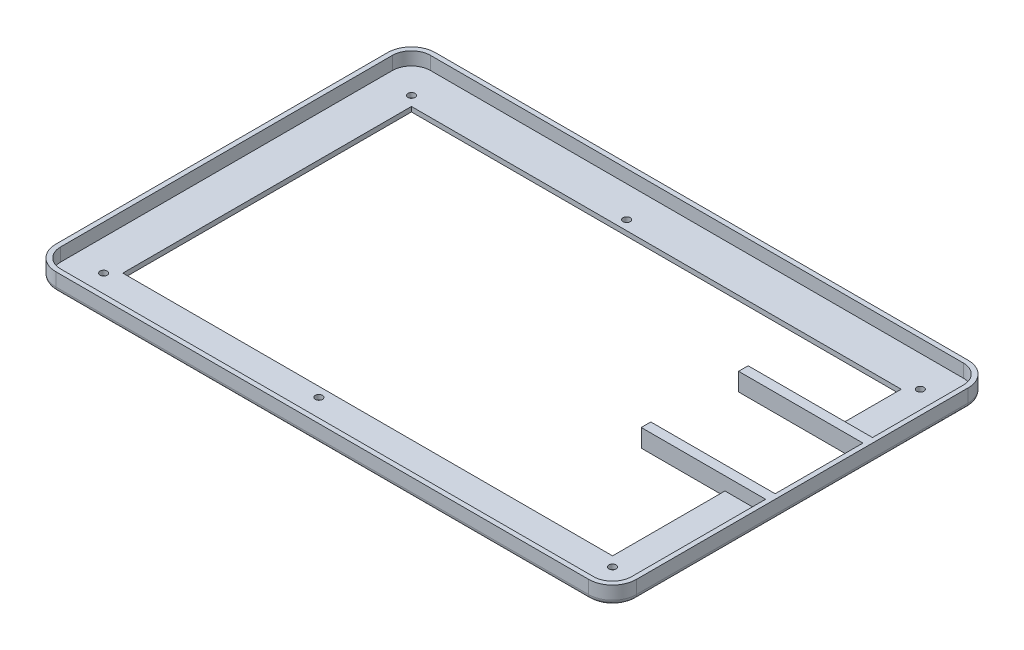
SolidWorks part; units mm, degrees
ref_plane "Ebene vorne" through (0, 0, 0) normal (0, 0, 1) x (1, 0, 0)
ref_plane "Ebene oben" through (0, 0, 0) normal (0, 1, 0) x (1, 0, 0)
ref_plane "Ebene rechts" through (0, 0, 0) normal (1, 0, 0) x (0, 0, -1)
sketch "Skizze1" plane through (0, 0, 0) normal (0, 1, 0) x (1, 0, 0)
  line L1 (0, 0) -> (242.8, 0)
  line L2 (0, 0) -> (0, 158.7)
  line L3 (0, 158.7) -> (242.8, 158.7)
  line L4 (242.8, 0) -> (242.8, 158.7)
  dimension "D1" = 242.8
  dimension "D2" = 158.7
extrude "Aufsatz-Linear austragen1" add sketch "Skizze1" along normal blind 7.5
fillet "Verrundung1" radius 10 4 edges at (0, 3.75, -158.7) (242.8, 3.75, -158.7) (0, 3.75, 0) (242.8, 3.75, 0)
shell "Wandung1" thickness 2 removed face at (121.4, 7.5, -79.35)
hole_wizard "Ø3.0 (3) Durchmesser Bohrung1" positions "Skizze3" profile "Skizze4" hole size "Ø3.0" standard "ANSI Metric"
sketch "Skizze3" plane through (0, 2, 0) normal (0, 1, 0) x (1, 0, 0)
  line L0 (232.8, 158.7) -> (10, 158.7) construction
  line L1 (0, 148.7) -> (0, 10) construction
  line L2 (10, 0) -> (232.8, 0) construction
  point P0 (15, 143.7)
  point P2 (105, 143.7)
  point P4 (227.8, 143.7)
  point P6 (227.8, 15)
  point P8 (105, 15)
  point P10 (15, 15)
  dimension "D1" = 90
  dimension "D2" = 122.8
  dimension "D3" = 15
  dimension "D4" = 15
  dimension "D5" = 15
sketch "Skizze4" plane through (15, 2, -143.7) normal (1, 0, 0) x (0, 0, 1)
  line L0 (0, 0) -> (0, 6.9013)
  line L1 (0, 6.9013) -> (1.5, 6)
  line L2 (1.5, 6) -> (1.5, 0)
  line L5 (1.5, 0) -> (0, 0)
  line L10 (0, 6.9013) -> (-1.5, 6) construction
  line L11 (0, -6.35) -> (0, 107.95) construction
  dimension "Bohrerdurchmesser" = 3
  dimension "Bohrungstiefe" = 6
  dimension "Spitzenwinkel" = 118
sketch "Skizze5" plane through (0, 2, 0) normal (0, 1, 0) x (1, 0, 0)
  line L0 (2, 148.7) -> (2, 10) construction
  line L1 (19, 139.7) -> (223.8, 139.7)
  line L2 (19, 139.7) -> (19, 19)
  line L3 (19, 19) -> (223.8, 19)
  line L4 (223.8, 139.7) -> (223.8, 19)
  line L5 (232.8, 156.7) -> (10, 156.7) construction
  line L6 (240.8, 10) -> (240.8, 148.7) construction
  line L7 (10, 2) -> (232.8, 2) construction
  dimension "D1" = 17
  dimension "D2" = 17
  dimension "D3" = 17
  dimension "D4" = 17
extrude "Schnitt-Linear austragen1" cut sketch "Skizze5" against normal through all
fillet "Verrundung2" radius 2 8 edges at (2.9289, 0, -2.9289) (0, 0, -79.35) (2.9289, 0, -155.7711) (121.4, 0, -158.7) (239.8711, 0, -155.7711) (242.8, 0, -79.35) (239.8711, 0, -2.9289) (121.4, 0, 0)
sketch "Skizze6" plane through (0, 0, 0) normal (0, -1, 0) x (1, 0, 0)
  line L0 (223.8, -19) -> (223.8, -139.7) construction
  line L1 (223.8, -70) -> (240.8, -70)
  line L2 (223.8, -70) -> (223.8, -106.7)
  line L3 (223.8, -106.7) -> (240.8, -106.7)
  line L4 (240.8, -70) -> (240.8, -106.7)
  line L6 (10, 0) -> (232.8, 0) construction
  line L7 (232.8, -158.7) -> (10, -158.7) construction
  dimension "D1" = 70
  dimension "D2" = 52
  dimension "D3" = 17
extrude "Schnitt-Linear austragen2" cut sketch "Skizze6" against normal blind 7.5
sketch "Skizze8" plane through (0, 2, 0) normal (0, 1, 0) x (1, 0, 0)
  line L0 (240.8, 106.7) -> (188.8, 106.7)
  line L10 (188.8, 70) -> (240.8, 70)
  line L11 (240.8, 70) -> (240.8, 66)
  line L12 (240.8, 10) -> (240.8, 70) construction
  line L13 (240.8, 66) -> (188.8, 66)
  line L15 (188.8, 110.7) -> (240.8, 110.7)
  line L16 (240.8, 106.7) -> (240.8, 148.7) construction
  line L17 (240.8, 110.7) -> (240.8, 106.7)
  line L18 (188.8, 110.7) -> (188.8, 106.7)
  line L19 (188.8, 70) -> (188.8, 66)
  dimension "D1" = 4
  dimension "D2" = 52
  dimension "D3" = 4
extrude "Aufsatz-Linear austragen2" add sketch "Skizze8" along normal up to surface (5.5 mm away) and the other way blind 2 up to face at (121.4, 7.5, -79.35)
equation "\"D1@Aufsatz-Linear austragen1\"=4.5+2+1"
